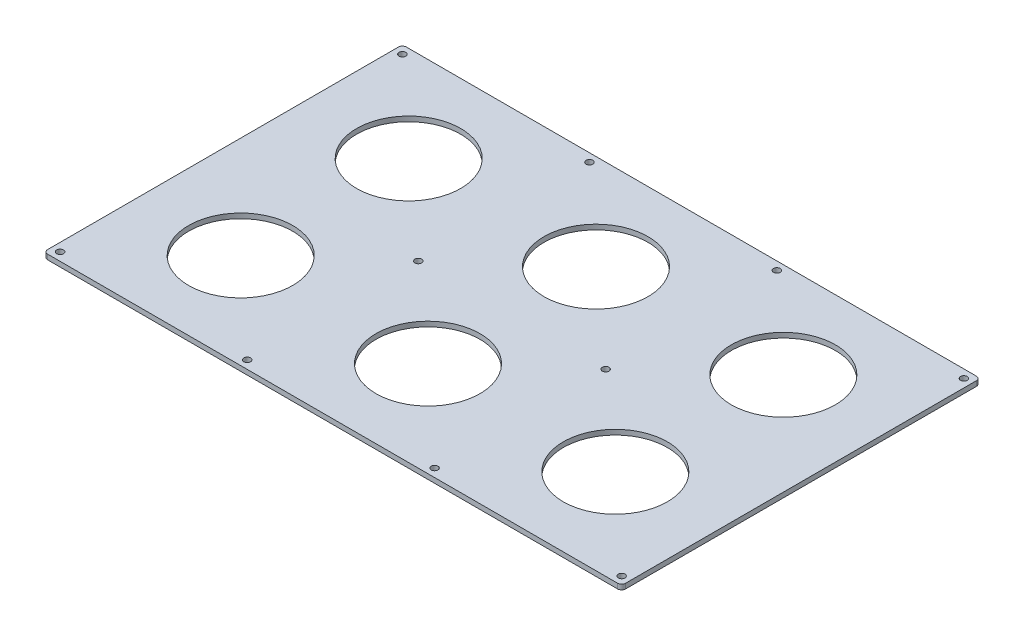
SolidWorks part; units mm, degrees
material "Acrylic (Medium-high impact)"
ref_plane "Front" through (0, 0, 0) normal (0, 0, 1) x (1, 0, 0)
ref_plane "Top" through (0, 0, 0) normal (0, 1, 0) x (1, 0, 0)
ref_plane "Right" through (0, 0, 0) normal (1, 0, 0) x (0, 0, -1)
sketch "Sketch1" plane through (0, 0, 0) normal (0, 1, 0) x (1, 0, 0)
  line L1 (-184.15, -114.3) -> (184.15, -114.3)
  line L2 (-184.15, -114.3) -> (-184.15, 114.3)
  line L3 (-184.15, 114.3) -> (184.15, 114.3)
  line L4 (184.15, -114.3) -> (184.15, 114.3)
  line L5 (-184.15, -114.3) -> (184.15, 114.3) construction
  line L6 (-184.15, 114.3) -> (184.15, -114.3) construction
  circle A0 centre (119.38, 53.5305) radius 33.147
  circle A1 centre (0, 53.5305) radius 33.147
  circle A2 centre (-119.38, 53.5305) radius 33.147
  circle A3 centre (-119.38, -53.5305) radius 33.147
  circle A4 centre (0, -53.5305) radius 33.147
  circle A5 centre (119.38, -53.5305) radius 33.147
  circle A6 centre (119.38, 53.5305) radius 33.02 construction
  point P0 (0, 0)
  dimension "D3" = 0.127
  dimension "D1" = 368.3
  dimension "D2" = 228.6
extrude "Boss-Extrude1" add sketch "Sketch1" along normal blind 3.175
fillet "Fillet1" radius 2.54 4 edges at (-184.15, 1.5875, 114.3) (184.15, 1.5875, 114.3) (184.15, 1.5875, -114.3) (-184.15, 1.5875, -114.3)
hole_wizard "#8 Clearance Hole1" positions "Sketch2" profile "Sketch3" hole size "#8" standard "ANSI Inch" end condition through all
sketch "Sketch2" plane through (0, 0, 0) normal (0, -1, 0) x (-1, 0, 0)
  point P0 (-178.9078, 109.0578)
  point P3 (-59.69, 109.0578)
  point P6 (59.69, 109.0578)
  point P9 (178.9078, 109.0578)
  point P12 (178.9078, -109.0578)
  point P15 (59.69, -109.0578)
  point P18 (-59.69, -109.0578)
  point P21 (-178.9078, -109.0578)
  point P26 (59.69, 0)
  point P30 (-59.69, 0)
sketch "Sketch3" plane through (178.9078, 0, -109.0578) normal (1, 0, 0) x (0, 0, -1)
  line L0 (0, 0) -> (0, 3.175)
  line L1 (0, 3.175) -> (2.1526, 3.175)
  line L2 (2.1526, 3.175) -> (2.1526, 0)
  line L5 (2.1526, 0) -> (0, 0)
  line L11 (0, -6.35) -> (0, 107.95) construction
  dimension "Thru Hole Dia." = 4.3053
  dimension "Thru Hole Depth" = 3.175
